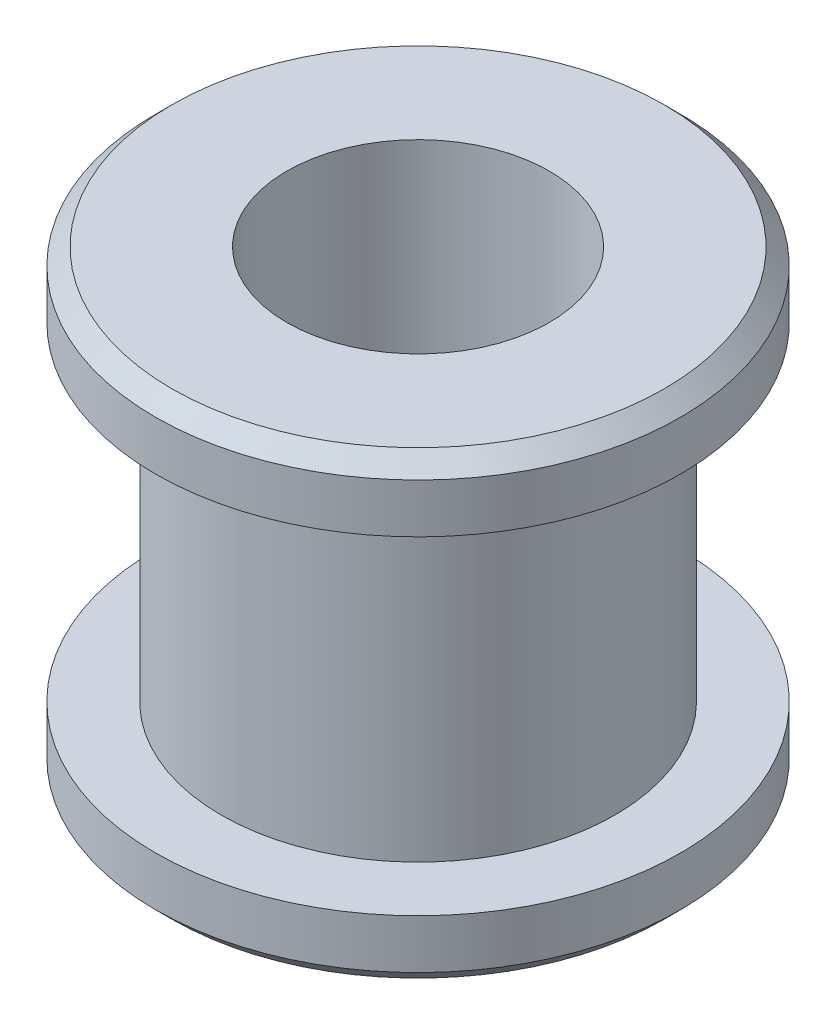
SolidWorks part; units mm, degrees
ref_plane "Front Plane" through (0, 0, 0) normal (0, 0, 1) x (1, 0, 0)
ref_plane "Top Plane" through (0, 0, 0) normal (0, 1, 0) x (1, 0, 0)
ref_plane "Right Plane" through (0, 0, 0) normal (1, 0, 0) x (0, 0, -1)
sketch "Sketch1" plane through (0, 0, 0) normal (0, 1, 0) x (1, 0, 0)
  circle A0 centre (0, 0) radius 6
  circle A1 centre (0, 0) radius 4
  circle A2 centre (0, 0) radius 8
extrude "Boss-Extrude1" add sketch "Sketch1" along normal blind 12 and the other way blind 2 contours A0 A1 region at (-5.8303, 0, 0)
extrude "Boss-Extrude2" add sketch "Sketch1<3>" against normal blind 2 contours A2 A0 region at (-7.7737, 0, 0)
sketch "Sketch1<3>" plane through (0, 0, 0) normal (0, 1, 0) x (1, 0, 0) same geometry as "Sketch1"
extrude "Boss-Extrude3" add sketch "Sketch1<4>" along normal blind 2 from offset 10 contours A2 A0 region at (-7.7737, 0, 0)
sketch "Sketch1<4>" plane through (0, 0, 0) normal (0, 1, 0) x (1, 0, 0) same geometry as "Sketch1"
chamfer "Chamfer1" distance 0.5 angle 45 2 edges at (0, -2, 8) (0, 12, 8)
